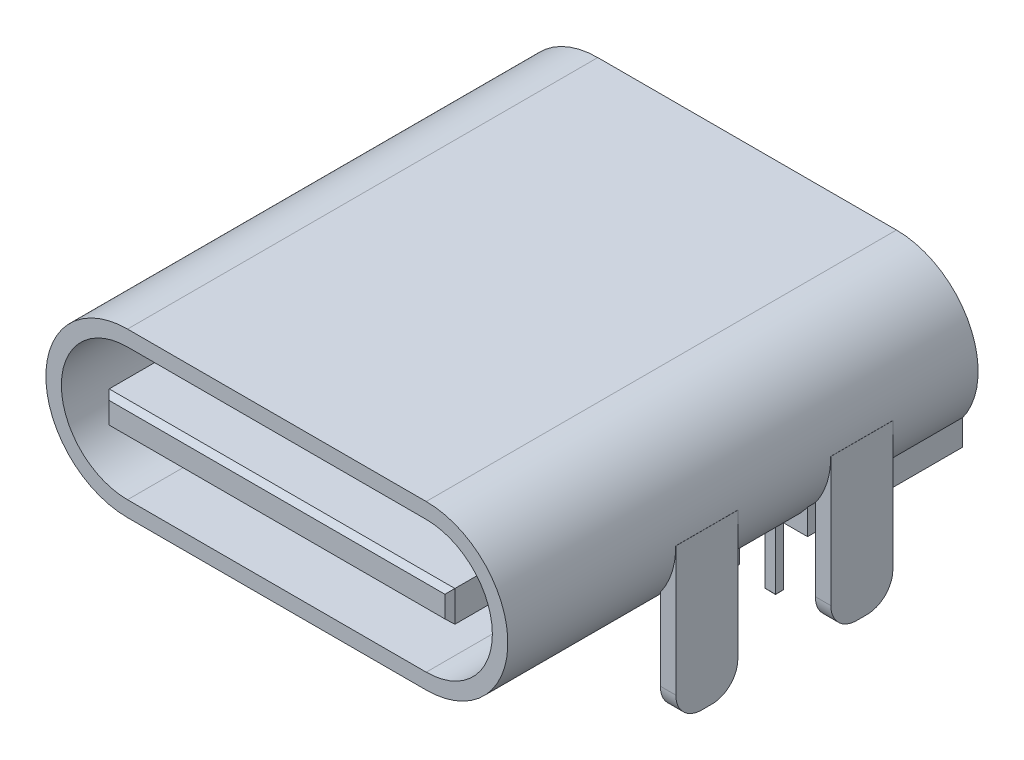
SolidWorks part; units mm, degrees
ref_plane "Front Plane" through (0, 0, 0) normal (0, 0, 1) x (1, 0, 0)
ref_plane "Top Plane" through (0, 0, 0) normal (0, 1, 0) x (1, 0, 0)
ref_plane "Right Plane" through (0, 0, 0) normal (1, 0, 0) x (0, 0, -1)
sketch "Sketch1" plane through (0, 0, 0) normal (0, 0, 1) x (1, 0, 0)
  line L0 (2.89, 0) -> (-2.89, 0) construction
  line L1 (2.89, 0) -> (2.89, 1.58) construction
  line L2 (-2.89, 0) -> (2.89, 0) construction
  line L3 (-2.89, 1.58) -> (2.89, 1.58)
  line L4 (-2.89, -1.58) -> (2.89, -1.58)
  line L5 (-2.89, 1.28) -> (2.89, 1.28)
  line L6 (-2.89, -1.28) -> (2.89, -1.28)
  line L8 (3.345, -0.3) -> (-3.345, -0.3)
  line L9 (3.345, -0.3) -> (3.345, 0.3)
  line L10 (3.345, 0.3) -> (-3.345, 0.3)
  line L11 (-3.345, -0.3) -> (-3.345, 0.3)
  line L12 (3.345, -0.3) -> (-3.345, 0.3) construction
  line L13 (3.345, 0.3) -> (-3.345, -0.3) construction
  arc A0 (-2.89, 1.58) -> (-2.89, -1.58) centre (-2.89, 0) ccw
  arc A1 (2.89, -1.58) -> (2.89, 1.58) centre (2.89, 0) ccw
  arc A2 (2.89, -1.28) -> (2.89, 1.28) centre (2.89, 0) ccw
  arc A3 (-2.89, 1.28) -> (-2.89, -1.28) centre (-2.89, 0) ccw
  point P0 (0, 0)
  point P4 (0, 0)
  point P16 (0, 0)
  dimension "D1" = 5.78
  dimension "D2" = 1.58
  dimension "D4" = 6.69
  dimension "D5" = 0.6
  dimension "D3" = 0.3
extrude "Boss-Extrude1" add sketch "Sketch1" against normal blind 9.1 contours L11 L8 L9 L10 | L4 A1 L3 A0 A3 L5 A2 L6 region at (0, 1.4852, 0) region at (0, 0, 0)
chamfer "Chamfer1" distance 0.1 angle 43 4 edges at (-3.345, 0, 0) (0, -0.3, 0) (3.345, 0, 0) (0, 0.3, 0) first distance on face at (-3.345, 0, -4.55) first distance on face at (0, -0.3, -4.55) first distance on face at (3.345, 0, -4.55) first distance on face at (0, 0.3, -4.55)
sketch "Sketch2" plane through (0, -1.58, 0) normal (0, -1, 0) x (1, 0, 0)
  line L1 (4.17, -9.1) -> (-4.17, -9.1)
  line L2 (4.17, -9.1) -> (4.17, -6.1)
  line L3 (4.17, -6.1) -> (-4.17, -6.1)
  line L4 (-4.17, -9.1) -> (-4.17, -6.1)
  line L5 (4.17, -9.1) -> (-4.17, -6.1) construction
  line L6 (4.17, -6.1) -> (-4.17, -9.1) construction
  line L7 (-2.89, -9.1) -> (2.89, -9.1) construction
  line L8 (-4.47, 0) -> (-4.47, -9.1) construction
  line L9 (4.47, -9.1) -> (4.47, 0) construction
  point P4 (0, -7.6)
  dimension "D1" = 3
  dimension "D2" = 0.3
  dimension "D3" = 0.3
extrude "Boss-Extrude2" add sketch "Sketch2" against normal up to surface (2.86 mm away) separate body up to face at (0, 1.28, -4.55)
fillet "Fillet1" radius 1.25 2 edges at (-4.17, 1.28, -7.6) (4.17, 1.28, -7.6)
sketch "Sketch4" plane through (-4.17, 0, 0) normal (-1, 0, 0) x (0, 0, 1)
  line L0 (0, 0) -> (-9.1, 0) construction
  line L1 (-6.75, -3) -> (-6.95, -3)
  line L2 (-6.25, -2.5) -> (-6.25, 0)
  line L3 (-6.25, 0) -> (-7.45, 0)
  line L4 (-7.45, -2.5) -> (-7.45, 0)
  line L5 (-6.25, -3) -> (-7.45, 0) construction
  line L6 (-6.25, 0) -> (-7.45, -3) construction
  line L7 (-9.1, 1.58) -> (-9.1, -1.58) construction
  arc A0 (-6.95, -3) -> (-7.45, -2.5) centre (-6.95, -2.5) cw
  arc A1 (-6.75, -3) -> (-6.25, -2.5) centre (-6.75, -2.5) ccw
  point P4 (-6.85, -1.5)
  dimension "D4" = 0.5
  dimension "D5" = 0.5
  dimension "D1" = 1.2
  dimension "D2" = 3
  dimension "D3" = 6.85
extrude "Boss-Extrude3" add sketch "Sketch4" along normal blind 0.3 separate body
pattern_linear "LPattern2" count 2 spacing 3 along (0, 0, 1) of "Boss-Extrude3"
pattern_linear "LPattern3" count 2 spacing 8.64 along (1, 0, 0) of "LPattern2", "Boss-Extrude3"
sketch "Sketch6" plane through (0, -1.58, 0) normal (0, -1, 0) x (1, 0, 0)
  line L0 (4.17, -6.1) -> (-4.17, -6.1) construction
  line L1 (4.17, -9.1) -> (-4.17, -9.1)
  line L2 (4.17, -9.1) -> (4.17, -6.1)
  line L3 (4.17, -6.1) -> (-4.17, -6.1)
  line L4 (-4.17, -9.1) -> (-4.17, -6.1)
  line L5 (4.17, -9.1) -> (-4.17, -6.1) construction
  line L6 (4.17, -6.1) -> (-4.17, -9.1) construction
  point P4 (0, -7.6)
extrude "Cut-Extrude1" cut sketch "Sketch6" against normal blind 0.16
sketch "Sketch7" plane through (0, -1.42, 0) normal (0, -1, 0) x (1, 0, 0)
  line L0 (0, 0) -> (0, -9.1) construction
  line L1 (-3.5828, -9.1) -> (3.5828, -9.1) construction
  line L2 (0, -8) -> (-0.425, -8) construction
  line L3 (-2.89, 0) -> (2.89, 0) construction
  line L5 (-0.325, -8.075) -> (-0.525, -8.075)
  line L6 (-0.325, -8.075) -> (-0.325, -7.925)
  line L7 (-0.325, -7.925) -> (-0.525, -7.925)
  line L8 (-0.525, -8.075) -> (-0.525, -7.925)
  line L9 (-0.325, -8.075) -> (-0.525, -7.925) construction
  line L10 (-0.325, -7.925) -> (-0.525, -8.075) construction
  dimension "D1" = 8
  dimension "D2" = 0.425
  dimension "D3" = 0.2
  dimension "D4" = 0.15
extrude "Boss-Extrude4" add sketch "Sketch7" along normal blind 1.8 separate body
chamfer "Chamfer2" distance 0.05 angle 43 4 edges at (-0.425, -3.22, -8.075) (-0.325, -3.22, -8) (-0.525, -3.22, -8) (-0.425, -3.22, -7.925) first distance on face at (-0.425, -2.32, -8.075) first distance on face at (-0.325, -2.32, -8) first distance on face at (-0.525, -2.32, -8) first distance on face at (-0.425, -2.32, -7.925)
pattern_linear "LPattern4" count 5 spacing 0.85 along (1, 0, 0) count 4 spacing 0.85 along (-1, 0, 0) of "Boss-Extrude4", "Chamfer2" pattern seed only yes
pattern_linear "LPattern8" count 2 spacing 1.35 along (0, 0, 1) of "Boss-Extrude4", "Chamfer2"
sketch "Sketch8" plane through (0, -3.22, 0) normal (0, -1, 0) x (1, 0, 0)
  line L0 (-2.975, -7.9716) -> (-2.975, -8.0284) construction
  line L1 (-2.9216, -7.9716) -> (-3.0284, -7.9716) construction
  line L2 (-3.0284, -8.0284) -> (-2.9216, -8.0284) construction
  line L3 (-2.125, -7.9716) -> (-2.125, -8.0284) construction
  line L4 (-2.0716, -7.9716) -> (-2.1784, -7.9716) construction
  line L5 (-2.1784, -8.0284) -> (-2.0716, -8.0284) construction
  point P6 (-2.975, -8)
  point P13 (-2.125, -8)
ref_axis "Axis1" through (-2.975, -1.7778, -8) along (0, -1, 0)
ref_axis "Axis2" through (-2.125, -1.8461, -8) along (0, -1, 0)
